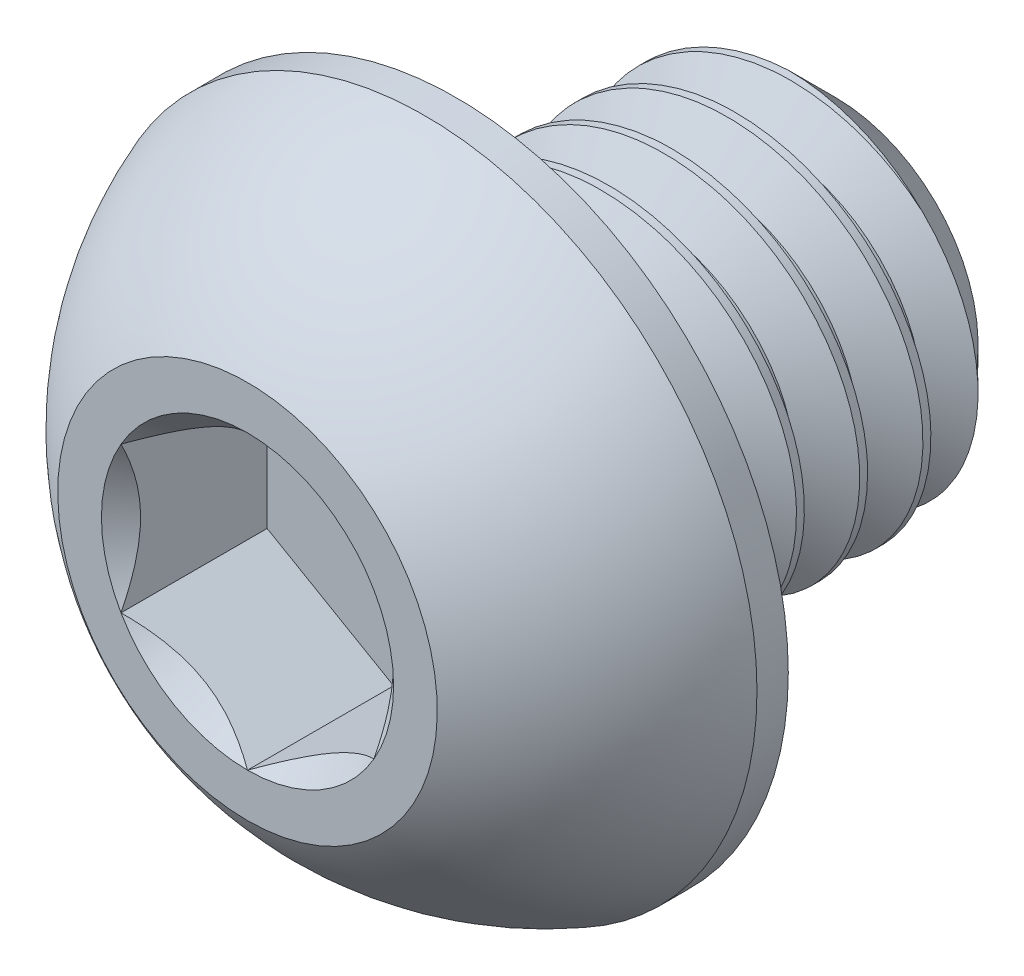
SolidWorks part; units mm, degrees
note: '?' marks a value the reader was unsure of.
ref_plane "Front" through (0, 0, 0) normal (0, 0, 1) x (1, 0, 0)
ref_plane "Top" through (0, 0, 0) normal (0, 1, 0) x (1, 0, 0)
ref_plane "Right" through (0, 0, 0) normal (1, 0, 0) x (0, 0, -1)
sketch "Sketch1" plane through (0, 0, 0) normal (1, 0, 0) x (0, 0, -1)
  line L2 (3.3, 3) -> (9.3, 3)
  line L3 (9.3, 3) -> (9.3, 0)
  line L4 (9.3, 0) -> (3.3, 0)
  line L6 (2.805, 5.25) -> (3.3, 5.25) construction
  line L7 (9.3, 3) -> (9.3, -3) construction
  line L8 (0, 0) -> (3.3, 0) construction
  line L9 (3.3, 5.25) -> (3.3, -5.25) construction
  line L11 (3.3, 3) -> (3.3, 0)
  line L13 (0, 2) -> (0, -2) construction
  line L14 (0, 2) -> (0, 3) construction
  arc A3 (0, 3) -> (2.805, 5.25) centre (4.7113, 0) cw construction
  dimension "D1" = 0.495
  dimension "Head Ht" = 3.3
  dimension "Head Dia" = 10.5
  dimension "Dia" = 6
  dimension "Lg" = 6
  dimension "Hex" = 4
revolve "Revolve1" add sketch "Sketch1" angle 360 mid plane about L4
sketch "Sketch3" plane through (0, 0, -9.3) normal (0, 0, -1) x (-1, 0, 0)
  circle A0 centre (0, 0) radius 3
curve "Helix/Spiral1" pitch 1 height 7 turns 7
chamfer "Chamfer1" distance 0.75 angle 45 1 edges at (0, 3, -9.3)
sketch "Sketch7" plane through (0, 0, 0) normal (1, 0, 0) x (0, 0, -1)
  line L6 (2.805, 5.25) -> (3.3, 5.25) construction
  line L8 (0, 0) -> (3.3, 0) construction
  line L11 (3.3, 5.25) -> (3.3, -5.25) construction
  line L12 (2.805, 5.25) -> (3.3, 5.25)
  line L13 (0, 0) -> (3.3, 0)
  line L14 (0, 2) -> (0, -2) construction
  line L15 (3.3, 5.25) -> (3.3, 0)
  line L16 (0, 3) -> (0, 0)
  arc A2 (2.805, 5.25) -> (0, 3) centre (4.7113, 0) ccw construction
  arc A3 (2.805, 5.25) -> (0, 3) centre (4.7113, 0) ccw
revolve "Revolve2" add sketch "Sketch7" angle 360 mid plane about L13
sketch "Sketch5" plane through (0, 0, 0) normal (0, 0, 1) x (1, 0, 0)
  line L1 (2, -1.1547) -> (2, 1.1547)
  line L2 (2, 1.1547) -> (0, 2.3094)
  line L3 (0, 2.3094) -> (-2, 1.1547)
  line L4 (-2, 1.1547) -> (-2, -1.1547)
  line L5 (-2, -1.1547) -> (0, -2.3094)
  line L6 (0, -2.3094) -> (2, -1.1547)
  circle A0 centre (0, 0) radius 2 construction
extrude "Cut-Extrude2" cut sketch "Sketch5" against normal blind 2.31
sketch "Sketch6" plane through (0, 0, 0) normal (0, 0, 1) x (1, 0, 0)
  circle A0 centre (0, 0) radius 2.3094
extrude "Cut-Extrude3" cut sketch "Sketch6" against normal blind 2.31 draft 45
sketch "Sketch2" plane through (0, 0, 0) normal (1, 0, 0) x (0, 0, -1)
  line L0 (8.55, 3) -> (9.425, 3)
  line L1 (9.425, 3) -> (9.05, 2.3505)
  line L2 (9.05, 2.3505) -> (8.925, 2.3505)
  line L3 (8.925, 2.3505) -> (8.55, 3)
  line L4 (8.7375, 2.6752) -> (9.2375, 2.6752) construction
  dimension "D1" = 60
  dimension "D2" = 0.125
  dimension "D3" = 0.5
sweep "Cut-Sweep1" cut profiles "Sketch2" path "Helix/Spiral1"
sketch "Sketch10" plane through (0, 0, 0) normal (1, 0, 0) x (0, 0, -1)
  line L0 (9.3, 3) -> (9.3, -3) construction
  point P0 (7.8, -3)
  dimension "D1" = 1.5
ref_axis "Center Axis 1" through (0, 0, -8.1113) along (0, 0, 1)?
ref_plane "Contact Plane 1" through (0, 0, -3.3) normal (0, 0, -1) x (-1, 0, 0)
ref_plane "Contact Plane 2" through (0, 0, 0) normal (0, 0, 1) x (1, 0, 0)
equation "\"D3@Helix/Spiral1\" = \"Lg@Sketch1\" + \"D4@Helix/Spiral1\""
equation "\"D2@Sketch2\" = \"D4@Helix/Spiral1\" * .125"
equation "\"D3@Sketch2\" = \"D4@Helix/Spiral1\" * .5"
equation "\"D1@Chamfer1\" = \"D4@Helix/Spiral1\" * .75"
equation "\"D1@Cut-Extrude2\" = \"Head Ht@Sketch1\" * .7"
equation "\"D1@Sketch1\" = \"Head Ht@Sketch1\" * .15"
equation "\"D1@Sketch10\" = \"D4@Helix/Spiral1\" * 1.5"
equation "\"D1@Cut-Extrude3\" = \"D1@Cut-Extrude2\""
